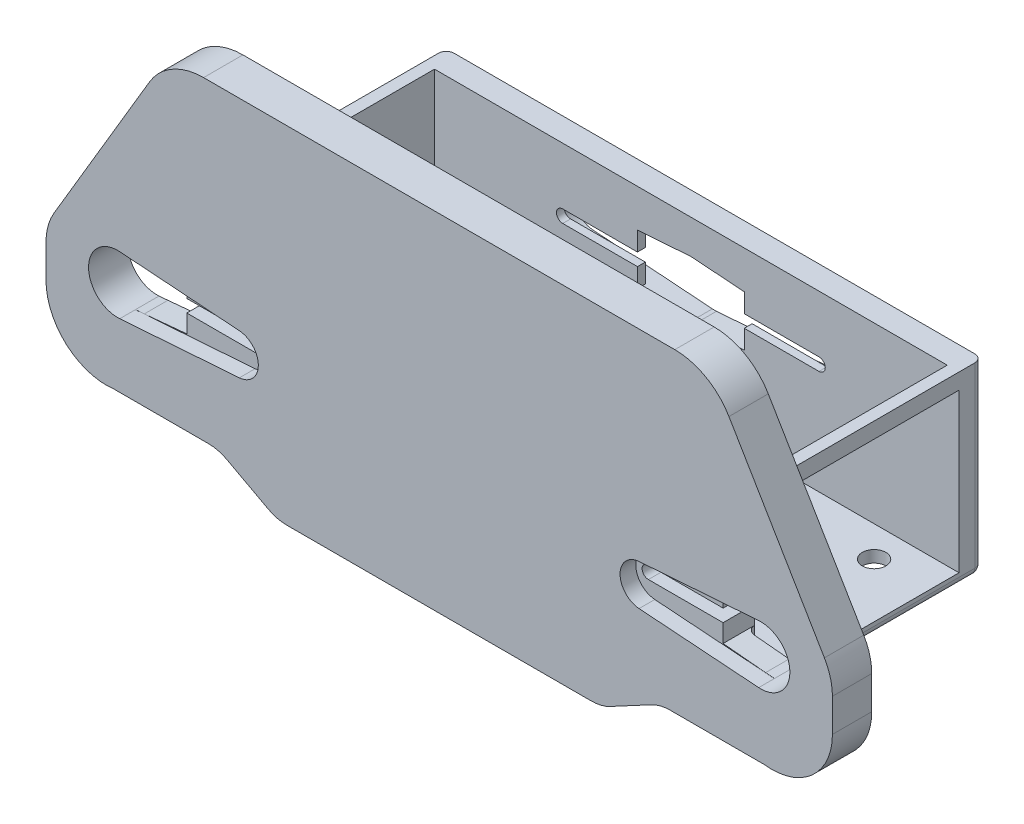
SolidWorks part; units mm, degrees
ref_plane "Front Plane" through (0, 0, 0) normal (0, 0, 1) x (1, 0, 0)
ref_plane "Top Plane" through (0, 0, 0) normal (0, 1, 0) x (1, 0, 0)
ref_plane "Right Plane" through (0, 0, 0) normal (1, 0, 0) x (0, 0, -1)
ref_plane "Plane1" through (0, 0, 0) normal (0, 0, -1) x (-1, 0, 0)
sketch "Sketch1" plane through (0, 0, 0) normal (0, 0, -1) x (-1, 0, 0)
  line L0 (0, 24.4289) -> (0, -19.5711) construction
  line L1 (-39.5, -0.1653) -> (-34.1, -0.6703)
  line L2 (-39.5, -3.7653) -> (-15.1934, -3.7653) construction
  line L3 (-34.1, -0.6703) -> (-34.1, -6.8603)
  line L4 (-34.1, -6.8603) -> (-39.5, -7.3653)
  line L5 (39.5, -0.1653) -> (34.1, -0.6703)
  line L6 (34.1, -0.6703) -> (34.1, -6.8603)
  line L7 (34.1, -6.8603) -> (39.5, -7.3653)
  line L28 (48.9808, 0) -> (36.8444, 20.5038)
  line L29 (29.96, 24.4289) -> (-29.96, 24.4289)
  line L30 (-36.8444, 20.5038) -> (-48.9808, 0)
  line L31 (-50, -3.7227) -> (-50, -7.9226)
  line L32 (-41.3074, -15.5711) -> (-29.3519, -15.5711)
  line L33 (-26.9929, -16.1626) -> (-21.7282, -18.9797)
  line L34 (-19.3692, -19.5711) -> (19.3692, -19.5711)
  line L35 (21.7282, -18.9797) -> (26.9929, -16.1626)
  line L36 (29.3519, -15.5711) -> (41.3074, -15.5711)
  line L37 (50, -7.9226) -> (50, -3.7227)
  line L38 (39.5, -3.7653) -> (39.5, -14.4393) construction
  line L39 (39.5, -3.7653) -> (30.9479, -3.7653) construction
  circle A5 centre (-39.5, -3.7653) radius 4 construction
  circle A7 centre (42, -8.7653) radius 0.75 construction
  circle A8 centre (37, -8.7653) radius 0.75 construction
  circle A9 centre (42, 1.2347) radius 0.75 construction
  circle A10 centre (39.5, -3.7653) radius 4 construction
  arc A11 (-39.5, -0.1653) -> (-39.5, -7.3653) centre (-39.5, -3.7653) ccw
  arc A12 (39.5, -0.1653) -> (39.5, -7.3653) centre (39.5, -3.7653) cw
  circle A15 centre (37, 1.2347) radius 0.75 construction
  arc A19 (50, -3.7227) -> (48.9808, 0) centre (42.6915, -3.7227) ccw
  arc A20 (36.8444, 20.5038) -> (29.96, 24.4289) centre (29.96, 16.4289) ccw
  arc A21 (-29.96, 24.4289) -> (-36.8444, 20.5038) centre (-29.96, 16.4289) ccw
  arc A22 (-48.9808, 0) -> (-50, -3.7227) centre (-42.6915, -3.7227) ccw
  arc A23 (-50, -7.9226) -> (-41.3074, -15.5711) centre (-42.2888, -7.9226) ccw
  arc A24 (-29.3519, -15.5711) -> (-26.9929, -16.1626) centre (-29.3519, -20.5711) cw
  arc A25 (-21.7282, -18.9797) -> (-19.3692, -19.5711) centre (-19.3692, -14.5711) ccw
  arc A26 (19.3692, -19.5711) -> (21.7282, -18.9797) centre (19.3692, -14.5711) ccw
  arc A27 (26.9929, -16.1626) -> (29.3519, -15.5711) centre (29.3519, -20.5711) cw
  arc A28 (41.3074, -15.5711) -> (50, -7.9226) centre (42.2888, -7.9226) ccw
  dimension "D2" = 8
  dimension "D4" = 7.3085
  dimension "D6" = 7.7112
  dimension "D8" = 5
  dimension "D10" = 5
  dimension "D12" = 5
  dimension "D14" = 5
  dimension "D16" = 7.7112
  dimension "D18" = 7.3085
  dimension "D20" = 8
  dimension "D27" = 8
  dimension "D28" = 1.5
  dimension "D29" = 7.2
  dimension "D3" = 20.5038
  dimension "D5" = 4.1999
  dimension "D7" = 11.9556
  dimension "D9" = 5.9711
  dimension "D13" = 5.9711
  dimension "D15" = 11.9556
  dimension "D17" = 4.1999
  dimension "D19" = 20.5038
  dimension "D21" = 10.5
  dimension "D23" = 5
  dimension "D24" = 11.8058
  dimension "D25" = 4
  dimension "D26" = 44
  dimension "D22" = 5
  dimension "D30" = 6.19
  dimension "D31" = 9
  dimension "D11" = 100
  dimension "D32" = 59.92
extrude "Boss-Extrude1" add sketch "Sketch1" against normal blind 5
sketch "Sketch7" plane through (0, 0, 5) normal (0, 0, 1) x (1, 0, 0)
  line L0 (-40.6238, -0.0749) -> (-25.4129, -1.1721)
  line L2 (-40.6238, -7.4558) -> (-25.4129, -6.3586)
  arc A1 (-40.6238, -0.0749) -> (-40.6238, -7.4558) centre (-40.89, -3.7653) ccw
  arc A2 (-25.4129, -1.1721) -> (-25.4129, -6.3586) centre (-25.6, -3.7653) cw
  circle A3 centre (-39.5, -3.7653) radius 3.6 construction
  arc A4 (-39.5, -0.1653) -> (-39.5, -7.3653) centre (-39.5, -3.7653) ccw construction
  dimension "D1" = 3.7
  dimension "D2" = 2.6
  dimension "D3" = 16.5
extrude "Cut-Extrude2" cut sketch "Sketch7" against normal offset from surface (2 mm away) 3 up to face at (37.7, -3.7653, 0)
sketch "Sketch8" plane through (0, 0, 3) normal (0, 0, 1) x (1, 0, 0)
  line L0 (-40.6238, -0.0749) -> (-39.5, -0.1653)
  line L1 (-40.6238, -7.4558) -> (-39.5, -7.3653)
  line L2 (-40.6238, -7.4558) -> (-25.4129, -6.3586)
  line L3 (-25.4129, -1.1721) -> (-40.6238, -0.0749)
  arc A0 (-39.5, -0.1653) -> (-39.5, -7.3653) centre (-39.5, -3.7653) ccw construction
  arc A1 (-39.5, -0.1653) -> (-39.5, -7.3653) centre (-39.5, -3.7653) ccw
  arc A2 (-40.6238, -0.0749) -> (-40.6238, -7.4558) centre (-40.89, -3.7653) ccw
  arc A3 (-25.4129, -6.3586) -> (-25.4129, -1.1721) centre (-25.6, -3.7653) ccw
  arc A4 (-40.6238, -0.0749) -> (-40.6238, -7.4558) centre (-40.89, -3.7653) ccw
  dimension "D1" = 0
extrude "Cut-Extrude3" cut sketch "Sketch8" against normal through all
sketch "Sketch9" plane through (0, 0, 3) normal (0, 0, 1) x (1, 0, 0)
  line L0 (-44.59, -3.7653) -> (-23, -3.7653) construction
  line L2 (-24.6, -2.9653) -> (-34.1, -2.9653)
  line L3 (-34.1, -6.8603) -> (-34.1, -0.6703) construction
  line L4 (-34.1, -2.9653) -> (-34.1, -4.5653)
  line L5 (-34.1, -4.5653) -> (-24.6, -4.5653)
  arc A0 (-40.6238, -0.0749) -> (-40.6238, -7.4558) centre (-40.89, -3.7653) ccw construction
  arc A1 (-25.4129, -6.3586) -> (-25.4129, -1.1721) centre (-25.6, -3.7653) ccw construction
  circle A3 centre (-24.6, -3.7653) radius 0.8 construction
  arc A4 (-24.6, -2.9653) -> (-24.6, -4.5653) centre (-24.6, -3.7653) cw
  dimension "D1" = 1.6
  dimension "D2" = 0.8
extrude "Cut-Extrude4" cut sketch "Sketch9" against normal through all
mirror "Mirror1" about plane through (0, 0, 0) normal (1, 0, 0) of "Cut-Extrude4", "Cut-Extrude3", "Cut-Extrude2"
sketch "Sketch12" plane through (0, 0, 0) normal (0, 0, -1) x (-1, 0, 0)
  line L0 (-40.89, -3.7653) -> (40.89, -3.7653) construction
  line L1 (-34.1, -2.9653) -> (-34.1, -0.6703) construction
  line L2 (34.1, -15.5711) -> (-34.1, -15.5711)
  line L3 (34.1, -15.5711) -> (34.1, 8.0405)
  line L4 (34.1, 8.0405) -> (-34.1, 8.0405)
  line L5 (-34.1, -15.5711) -> (-34.1, 8.0405)
  line L6 (34.1, -15.5711) -> (-34.1, 8.0405) construction
  line L7 (34.1, 8.0405) -> (-34.1, -15.5711) construction
  line L8 (-41.3074, -15.5711) -> (-29.3519, -15.5711) construction
  point P4 (0, -3.7653)
extrude "Boss-Extrude2" add sketch "Sketch12" along normal blind 30
sketch "Sketch13" plane through (0, 8.0405, 0) normal (0, 1, 0) x (1, 0, 0)
  line L1 (32.6, 0) -> (-32.6, 0)
  line L2 (32.6, 0) -> (32.6, 27)
  line L3 (32.6, 27) -> (-32.6, 27)
  line L4 (-32.6, 0) -> (-32.6, 27)
  line L5 (32.6, 0) -> (-32.6, 27) construction
  line L6 (32.6, 27) -> (-32.6, 0) construction
  line L7 (-29.96, 0) -> (29.96, 0) construction
  line L8 (-34.1, 30) -> (-34.1, 0) construction
  line L9 (34.1, 30) -> (34.1, 0) construction
  point P0 (0, 13.5)
  dimension "D1" = 27
  dimension "D2" = 1.5
  dimension "D3" = 1.5
extrude "Cut-Extrude5" cut sketch "Sketch13" against normal offset from surface (22.1116 mm away) 1.5 up to face at (0, -15.5711, -3.3333)
fillet "Fillet1" radius 1 10 edges at (-37.7037, -15.5711, 0) (34.1, 3.6851, 0) (34.1, -11.2157, 0) (34.1, -15.5711, -15) (-34.1, -11.2157, 0) (-34.1, -15.5711, -15) (34.1, -3.7653, -30) (0, -15.5711, -30) (-34.1, -3.7653, -30) (37.7037, -15.5711, 0)
fillet "Fillet2" radius 4 7 edges at (0, -15.5711, 0) (-28.1359, -15.7213, 0) (-24.3606, -17.5711, 0) (-20.5852, -19.421, 0) (20.5852, -19.421, 0) (24.3606, -17.5711, 0) (28.1359, -15.7213, 0)
sketch "Sketch14" plane through (0, -14.0711, 0) normal (0, 1, 0) x (1, 0, 0)
  line L0 (0, 0) -> (0, 27) construction
  line L1 (-32.6, 0) -> (32.6, 0) construction
  line L2 (32.6, 27) -> (-32.6, 27) construction
  line L3 (0, 13.5) -> (-32.6, 13.5) construction
  line L4 (-32.6, 27) -> (-32.6, 0) construction
  circle A0 centre (27.2, 23.1) radius 1.5
  circle A1 centre (-27.2, 23.1) radius 1.5
  circle A2 centre (27.2, 3.9) radius 1.5
  circle A3 centre (-27.2, 3.9) radius 1.5
  dimension "D1" = 3
  dimension "D2" = 16.2
  dimension "D3" = 52.9
extrude "Cut-Extrude6" cut sketch "Sketch14" against normal through all
sketch "Sketch15" plane through (34.1, 0, 0) normal (1, 0, 0) x (0, 0, -1)
  line L0 (29, 8.0405) -> (1, 8.0405) construction
  line L1 (1, 6.0405) -> (27, 6.0405)
  line L2 (1, 6.0405) -> (1, -14.0711)
  line L3 (1, -14.0711) -> (27, -14.0711)
  line L4 (27, 6.0405) -> (27, -14.0711)
  line L5 (1, 6.0405) -> (27, -14.0711) construction
  line L6 (1, -14.0711) -> (27, 6.0405) construction
  line L7 (29, -15.5711) -> (1, -15.5711) construction
  line L8 (0, -0.5768) -> (0, 8.0405) construction
  point P0 (14, -4.0153)
  dimension "D1" = 1
  dimension "D2" = 2
  dimension "D3" = 1.5
extrude "Cut-Extrude7" cut sketch "Sketch15" against normal up to next
sketch "Sketch16" plane through (0, 0, -30) normal (0, 0, -1) x (-1, 0, 0)
  line L0 (-40.89, -3.7653) -> (40.89, -3.7653) construction
  line L1 (0.2662, 3.6904) -> (15.4771, 2.5933)
  line L2 (0.2662, -3.6904) -> (15.4771, -2.5933)
  arc A0 (0.2662, 3.6904) -> (0.2662, -3.6904) centre (0, 0) ccw
  arc A1 (15.4771, 2.5933) -> (15.4771, -2.5933) centre (15.29, 0) cw
  circle A2 centre (1.39, 0) radius 3.6 construction
  dimension "D1" = 3.7
  dimension "D3" = 2.6
  dimension "D4" = 7.2
  dimension "D2" = 16.5
extrude "Cut-Extrude8" cut sketch "Sketch16" against normal blind 2
sketch "Sketch19" plane through (0, 0, -28) normal (0, 0, -1) x (-1, 0, 0)
  line L0 (6.79, 0.8) -> (16.29, 0.8)
  line L1 (16.29, -0.8) -> (6.79, -0.8)
  line L2 (6.79, -0.8) -> (6.79, 0.8)
  line L3 (0, 0) -> (6.79, 0) construction
  arc A0 (16.29, 0.8) -> (16.29, -0.8) centre (16.29, 0) cw
  arc A3 (15.4771, -2.5933) -> (15.4771, 2.5933) centre (15.29, 0) ccw construction
  circle A4 centre (16.29, 0) radius 0.8 construction
  dimension "D2" = 1.6
  dimension "D3" = 0.8
  dimension "D1" = 9.5
extrude "Cut-Extrude9" cut sketch "Sketch19" against normal up to surface (1 mm away) up to face at (11.3667, 0.0033, -27)
sketch "Sketch20" plane through (0, 0, -28) normal (0, 0, -1) x (-1, 0, 0)
  line L0 (6.79, 3.2199) -> (6.79, -3.2199)
  line L2 (0.2662, -3.6904) -> (15.4771, -2.5933)
  line L3 (15.4771, 2.5933) -> (0.2662, 3.6904)
  line L4 (0.2662, -3.6904) -> (6.79, -3.2199)
  line L5 (6.79, 3.2199) -> (0.2662, 3.6904)
  arc A2 (0.2662, 3.6904) -> (0.2662, -3.6904) centre (0, 0) ccw
  arc A3 (15.4771, -2.5933) -> (15.4771, 2.5933) centre (15.29, 0) ccw
  arc A4 (0.2662, 3.6904) -> (0.2662, -3.6904) centre (0, 0) ccw
  dimension "D1" = 0
extrude "Cut-Extrude10" cut sketch "Sketch20" against normal up to surface (1 mm away) up to face at (-11.74, 0, -27)
mirror "Mirror2" about plane through (0, 0, 0) normal (1, 0, 0) of "Cut-Extrude8", "Cut-Extrude10", "Cut-Extrude9"
equation "\"Ancho\"= 100"
equation "\"D11@Sketch1\"=\"Ancho\""
equation "\"D32@Sketch1\"=\"Ancho\"*0.5992"
